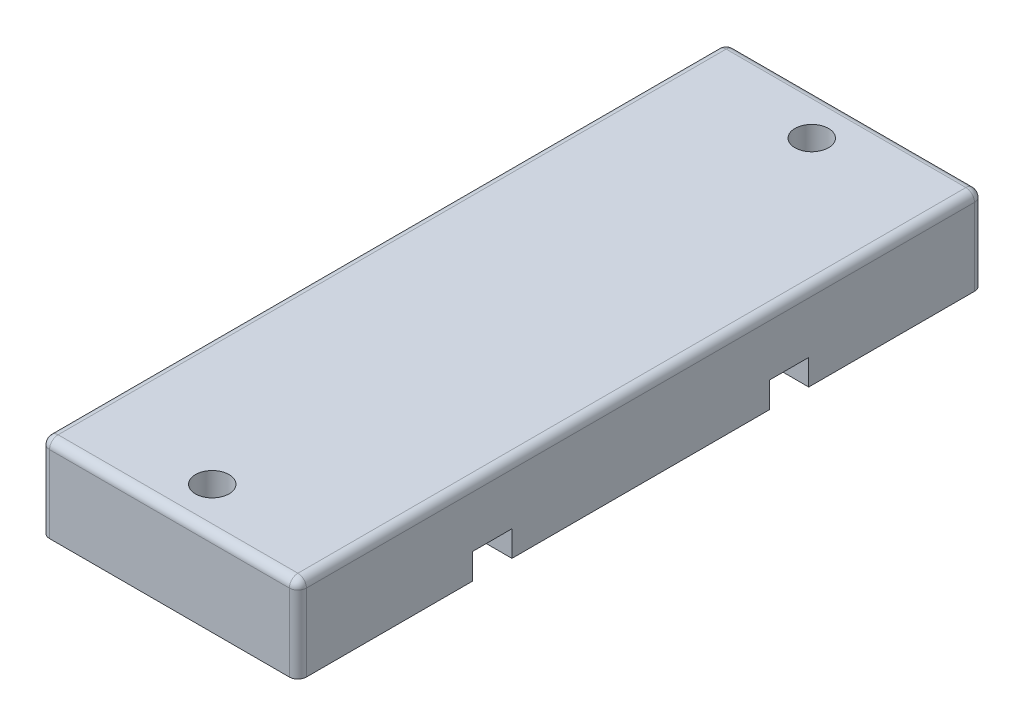
SolidWorks part; units mm, degrees
ref_plane "Front Plane" through (0, 0, 0) normal (0, 0, 1) x (1, 0, 0)
ref_plane "Top Plane" through (0, 0, 0) normal (0, 1, 0) x (1, 0, 0)
ref_plane "Right Plane" through (0, 0, 0) normal (1, 0, 0) x (0, 0, -1)
sketch "Sketch1" plane through (0, 0, 0) normal (0, 1, 0) x (1, 0, 0)
  line L4 (0, 101.6) -> (38.1, 101.6)
  line L5 (0, 101.6) -> (0, 117.8149) construction
  line L6 (38.1, 117.8149) -> (38.1, -40.9351) construction
  line L7 (38.1, 101.6) -> (38.1, 0)
  line L8 (38.1, 0) -> (0, 0)
  line L9 (0, 0) -> (0, 101.6)
extrude "Boss-Extrude1" add sketch "Sketch1" along normal blind 12.7
sketch "Sketch9" plane through (0, 12.7, 0) normal (0, 1, 0) x (1, 0, 0)
  line L0 (19.05, 0) -> (19.05, 6.35) construction
  line L1 (0, 0) -> (38.1, 0) construction
  line L2 (19.05, 101.6) -> (19.05, 95.25) construction
  line L3 (38.1, 101.6) -> (0, 101.6) construction
sketch "Sketch12" plane through (0, 0, 0) normal (-1, 0, 0) x (0, 0, 1)
  line L0 (-101.6, 0) -> (-75.7538, 0) construction
  line L1 (-101.6, 0) -> (0, 0) construction
  line L2 (-75.7538, 0) -> (-69.9156, 0) construction
  line L3 (-69.9156, 0) -> (-31.741, 0) construction
  line L4 (-31.741, 0) -> (-25.9028, 0) construction
  line L5 (-75.7538, 0) -> (-75.7538, 3.81)
  line L6 (-75.7538, 3.81) -> (-69.9156, 3.81)
  line L7 (-69.9156, 3.81) -> (-69.9156, 0)
  line L8 (-69.9156, 0) -> (-75.7538, 0)
  line L9 (-31.741, 0) -> (-31.741, 3.81)
  line L10 (-31.741, 3.81) -> (-25.9028, 3.81)
  line L11 (-25.9028, 3.81) -> (-25.9028, 0)
  line L12 (-25.9028, 0) -> (-31.741, 0)
  dimension "D1" = 5.8383
  dimension "D2" = 5.8383
extrude "Cut-Extrude1" cut sketch "Sketch12" against normal through all
fillet "Fillet2" radius 1.27 8 edges at (38.1, 6.35, -101.6) (38.1, 12.7, -50.8) (38.1, 6.35, 0) (19.05, 12.7, 0) (0, 6.35, 0) (19.05, 12.7, -101.6) (0, 12.7, -50.8) (0, 6.35, -101.6)
sketch "Sketch4" plane through (0, 12.7, 0) normal (0, 1, 0) x (1, 0, 0)
  line L0 (19.05, 0) -> (19.05, 6.35) construction
  line L2 (19.05, 101.6) -> (19.05, 95.25) construction
hole_wizard "#10 (0.1935) Diameter Hole2" positions "Sketch7" profile "Sketch8" hole size "#10" standard "ANSI Inch" end condition through all
sketch "Sketch7" plane through (0, 12.7, 0) normal (0, 1, 0) x (1, 0, 0)
  point P0 (19.05, 95.25)
  point P3 (19.05, 6.35)
sketch "Sketch8" plane through (19.05, 12.7, -95.25) normal (1, 0, 0) x (0, 0, 1)
  line L0 (0, 0) -> (0, 12.7)
  line L1 (0, 12.7) -> (2.4892, 12.7)
  line L2 (2.4892, 12.7) -> (2.4892, 0)
  line L5 (2.4892, 0) -> (0, 0)
  line L11 (0, -6.35) -> (0, 107.95) construction
  dimension "Thru Hole Dia." = 4.9784
  dimension "Thru Hole Depth" = 12.7
